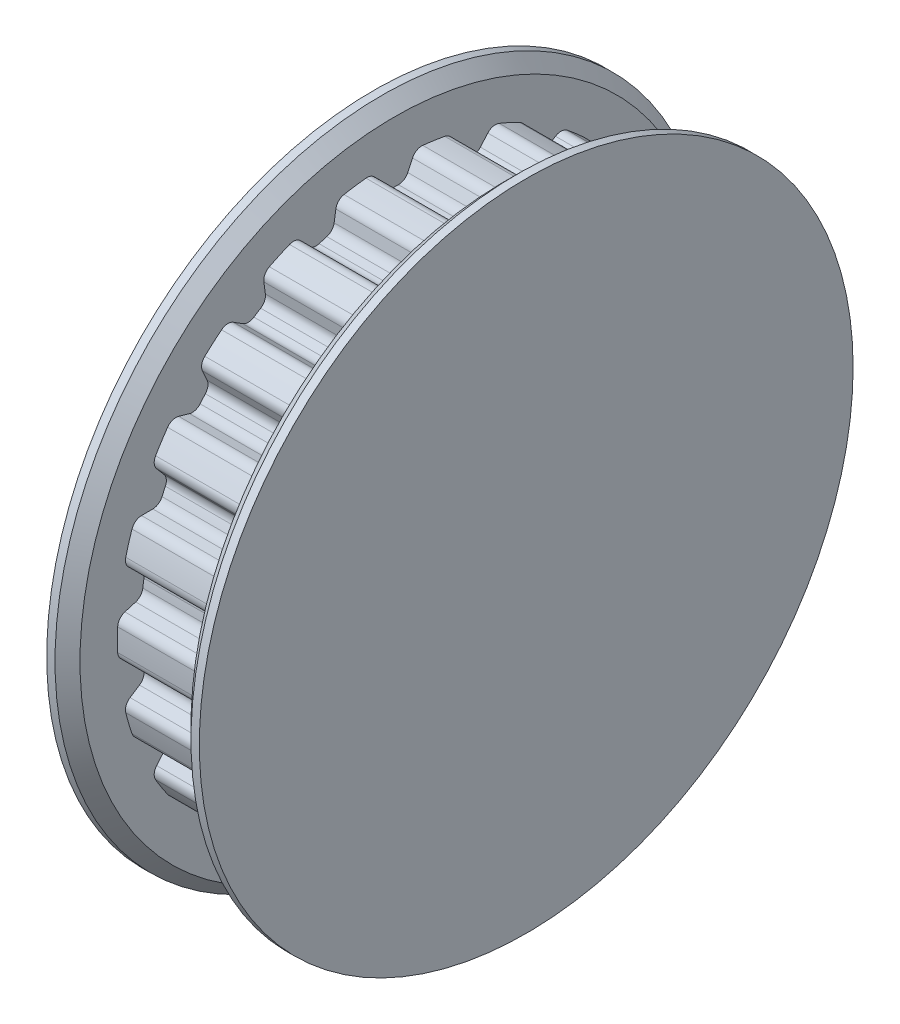
SolidWorks part; units mm, degrees
ref_plane "Front Plane" through (0, 0, 0) normal (0, 0, 1) x (1, 0, 0)
ref_plane "Top Plane" through (0, 0, 0) normal (0, 1, 0) x (1, 0, 0)
ref_plane "Right Plane" through (0, 0, 0) normal (1, 0, 0) x (0, 0, -1)
sketch "Sketch3" plane through (0, 0, 0) normal (1, 0, 0) x (0, 0, -1)
  circle A0 centre (0, 0) radius 16.6372
  dimension "D1" = 33.2743
extrude "Boss-Extrude1" add sketch "Sketch3" along normal mid plane 6.6675
sketch "Sketch4" plane through (0, 0, 0) normal (1, 0, 0) x (0, 0, -1)
  line L0 (0, 0) -> (0, 21.2108) construction
  line L1 (-1.2713, 16.5885) -> (-0.635, 15.2239)
  line L2 (1.2713, 16.5885) -> (0.635, 15.2239)
  circle A0 centre (0, 0) radius 16.6372 construction
  circle A1 centre (0, 0) radius 16.6372 construction
  circle A2 centre (0, 0) radius 15.2372 construction
  arc A3 (-0.635, 15.2239) -> (0.635, 15.2239) centre (0, 0) cw
  arc A4 (-1.2713, 16.5885) -> (1.2713, 16.5885) centre (0, 0) cw
  dimension "D1" = 1.4
  dimension "D2" = 1.27
  dimension "D3" = 25
extrude "Cut-Extrude1" cut sketch "Sketch4" against normal mid plane 11
fillet "Fillet1" radius 0.61 4 edges at (0, 16.5885, -1.2713) (0, 16.5885, 1.2713) (0, 15.2239, -0.635) (0, 15.2239, 0.635)
pattern_circular "CirPattern1" count 22 over 360 about axis through (3.3338, 0, 0) along (1, 0, 0) of "Cut-Extrude1", "Fillet1"
sketch "Sketch8" plane through (0, 0, 0) normal (1, 0, 0) x (0, 0, -1)
  circle A0 centre (0, 0) radius 19.6372
  dimension "D1" = 39.2743
extrude "Boss-Extrude4" add sketch "Sketch8" along normal blind 1.25 from surface starting at face at (3.3338, 0, 0)
extrude "Boss-Extrude5" add sketch "Sketch8<2>" against normal blind 1.25 from surface starting at face at (-3.3338, 0, 0)
sketch "Sketch8<2>" plane through (0, 0, 0) normal (1, 0, 0) x (0, 0, -1) same geometry as "Sketch8"
chamfer "Chamfer1" distance 0.75 angle 45 2 edges at (3.3338, 0, -19.6372) (-3.3338, 0, -19.6372)
equation "\"Number_of_Teeth\"= 22"
equation "\"D1@CirPattern1\"=\"Number_of_Teeth\""
equation "\"D1@Sketch3\"=\"Number_of_Teeth\" * 5.08 / pi-2.3"
equation "\"D1@Sketch8\"=\"D1@Sketch3\"+6"
equation "\"Belt_Thickness\"= .25in"
equation "\"D1@Boss-Extrude1\"=\"Belt_Thickness\"*1.05"
